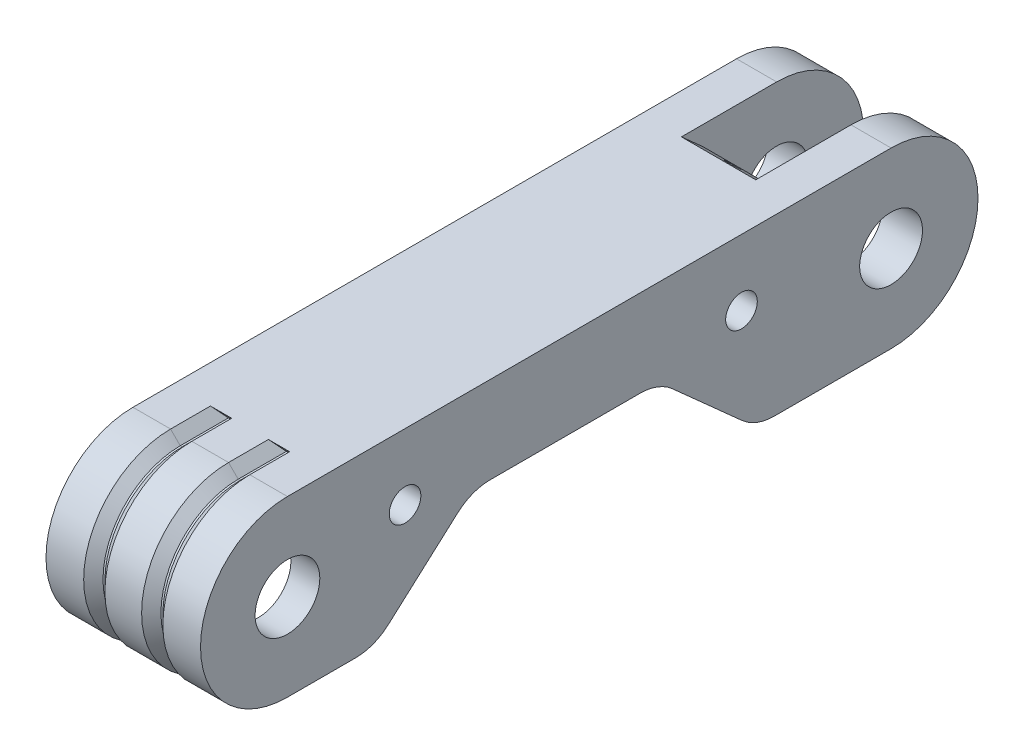
SolidWorks part; units mm, degrees
material "ABS"
ref_plane "Front Plane" through (0, 0, 0) normal (0, 0, 1) x (1, 0, 0)
ref_plane "Top Plane" through (0, 0, 0) normal (0, 1, 0) x (1, 0, 0)
ref_plane "Right Plane" through (0, 0, 0) normal (1, 0, 0) x (0, 0, -1)
ref_plane "Plane4" through (-3, 0, 0) normal (1, 0, 0) x (0, 0, -1)
sketch "Sketch1" plane through (0, 0, 0) normal (1, 0, 0) x (0, 0, -1)
  line L0 (0, 0) -> (62.5, 0) construction
  line L1 (0, 9) -> (62.5, 9)
  line L2 (0, -9) -> (62.5, -9)
  circle A0 centre (0, 0) radius 3.35
  circle A1 centre (62.5, 0) radius 3.25
  arc A2 (0, 9) -> (0, -9) centre (0, 0) ccw
  arc A3 (62.5, 9) -> (62.5, -9) centre (62.5, 0) cw
  dimension "D1" = 6.7
  dimension "D4" = 6.5
  dimension "D2" = 62.5
  dimension "D3" = 18
extrude "Finger Frame" add sketch "Sketch1" along normal mid plane 16
sketch "Sketch2" plane through (0, 0, 0) normal (1, 0, 0) x (0, 0, -1)
  line L0 (62.5, 9) -> (0, 9) construction
  line L1 (62.5, 9) -> (0, 9) construction
  line L2 (52.6402, 9) -> (55.6217, 6.3333)
  line L3 (62.5, 0) -> (0, 0) construction
  line L4 (62.5, 0) -> (55.8886, -6.6114) construction
  line L5 (55.8886, -6.6114) -> (53.15, -9.35)
  line L6 (53.15, -9.35) -> (62.5, -9.35)
  line L7 (62.5, 9.35) -> (52.6402, 9.35)
  line L8 (52.6402, 9.35) -> (52.6402, 9)
  circle A0 centre (62.5, 0) radius 9 construction
  arc A1 (62.5, -9) -> (62.5, 9) centre (62.5, 0) ccw construction
  circle A2 centre (62.5, 0) radius 9.35 construction
  arc A3 (55.6217, 6.3333) -> (55.8886, -6.6114) centre (62.5, 0) ccw
  arc A4 (62.5, 9.35) -> (62.5, -9.35) centre (62.5, 0) cw
  point P11 (53.7583, 8)
  dimension "D1" = 0.35
  dimension "D2" = 8
  dimension "D3" = 1.5
  dimension "D4" = 45
  dimension "D5" = 2.5
extrude "Routing Feature" cut sketch "Sketch2" against normal mid plane 7.7
sketch "Sketch3" plane through (8, 0, 0) normal (1, 0, 0) x (0, 0, -1)
  line L0 (52.6402, 9) -> (55.6217, 6.3333) construction
  line L1 (52.6402, 9) -> (55.6217, 6.3333) construction
  line L2 (54.131, 7.6667) -> (38.6499, -9.6417) construction
  line L3 (12.175, 2.1625) -> (47.0109, 2.1625) construction
  line L4 (62.5, 9) -> (0, 9) construction
  circle A0 centre (47.0109, 2.1625) radius 1.6375
  circle A1 centre (12.175, 2.1625) radius 1.6375
  arc A2 (55.6217, 6.3333) -> (55.8886, -6.6114) centre (62.5, 0) ccw construction
  arc A3 (55.6217, 6.3333) -> (55.8886, -6.6114) centre (62.5, 0) ccw construction
  circle A4 centre (0, 0) radius 9 construction
  arc A5 (0, 9) -> (0, -9) centre (0, 0) ccw construction
  point P19 (10.5375, 2.1625)
  point P20 (9, 0)
  dimension "D1" = 3.275
  dimension "D2" = 6.8375
  dimension "D3" = 3.175
extrude "Routing Pins" cut sketch "Sketch3" against normal through all
sketch "Sketch7" plane through (0, 31.1571, -27.8678) normal (0, 0.7454, -0.6667) x (1, 0, 0)
  line L0 (0, 33.2357) -> (0, 37.2357) construction
  line L1 (-3.85, 33.2357) -> (3.85, 33.2357) construction
  line L2 (-3.85, 37.2357) -> (3.85, 37.2357) construction
  circle A0 centre (0, 34.7357) radius 0.75
  dimension "D2" = 1.5
  dimension "D1" = 1.5
extrude "Tendon Port" [suppressed] cut sketch "Sketch7" against normal blind 0.75
chamfer "Tendon Port Chamfer" [suppressed] distance 0.75 angle 45
sketch "Sketch6" plane through (8, 0, 0) normal (1, 0, 0) x (0, 0, -1)
  line L0 (62.5, 9) -> (0, 9) construction
  line L1 (11.95, 11.95) -> (47.3902, 11.95)
  line L2 (9, 9) -> (50.3402, 9)
  line L3 (9, 0) -> (9, 9) construction
  line L4 (52.6402, 9) -> (55.6217, 6.3333) construction
  line L5 (52.6402, 9) -> (55.6217, 6.3333) construction
  arc A0 (9, 9) -> (11.95, 11.95) centre (11.95, 9) cw
  arc A1 (47.3902, 11.95) -> (50.3402, 9) centre (47.3902, 9) cw
  circle A2 centre (0, 0) radius 9 construction
  arc A3 (0, 9) -> (0, -9) centre (0, 0) ccw construction
  dimension "D1" = 2.95
  dimension "D2" = 2.3
extrude "Finger Pad Outline" add sketch "Sketch6" against normal up to surface (16 mm away) up to face at (-8, 2.1625, -13.8125)
sketch "Sketch5" plane through (8, 0, 0) normal (1, 0, 0) x (0, 0, -1)
  line L0 (9, -9) -> (19.0623, 0)
  line L1 (0, -9) -> (62.5, -9) construction
  line L2 (19.0623, 0) -> (38.4377, 0)
  line L3 (38.4377, 0) -> (48.5, -9)
  line L4 (48.5, -9) -> (9, -9)
  line L5 (12.175, 2.1625) -> (47.0109, 2.1625) construction
  line L6 (29.593, 2.1625) -> (29.593, 9) construction
  line L7 (62.5, 9) -> (50.3402, 9) construction
  line L8 (52.6402, 9) -> (55.6217, 6.3333) construction
  line L9 (52.6402, 9) -> (55.6217, 6.3333) construction
  line L10 (19.0623, 0) -> (0, 0) construction
  line L11 (9, 9) -> (9, -9) construction
  line L12 (53.5, -9) -> (62.5, -9) construction
  line L13 (53.5, -9) -> (62.5, -9) construction
  dimension "D1" = 5
extrude "Finger Outline" cut sketch "Sketch5" against normal through all
sketch "Sketch10" plane through (0, 0, 0) normal (1, 0, 0) x (0, 0, -1)
  line L0 (0, -5) -> (0, -9)
  line L1 (0.5007, 4.9749) -> (12.175, 3.8)
  line L2 (12.175, 3.8) -> (47.0109, 3.8)
  line L3 (48.5497, 1.6024) -> (44.6907, -9)
  line L4 (44.6907, -9) -> (0, -9)
  circle A0 centre (12.175, 2.1625) radius 1.6375 construction
  circle A1 centre (47.0109, 2.1625) radius 1.6375 construction
  circle A2 centre (12.175, 2.1625) radius 1.6375 construction
  arc A3 (48.5497, 1.6024) -> (47.0109, 3.8) centre (47.0109, 2.1625) ccw
  circle A4 centre (0, 0) radius 3.35 construction
  circle A5 centre (0, 0) radius 3.35 construction
  circle A6 centre (0, 0) radius 5 construction
  circle A7 centre (0, 0) radius 9 construction
  arc A8 (0, 9) -> (0, -9) centre (0, 0) ccw construction
  arc A9 (0, -5) -> (0.5007, 4.9749) centre (0, 0) cw
  dimension "D1" = 10
  dimension "D2" = 70
extrude "Back Cutaway" cut sketch "Sketch10" against normal mid plane 10
sketch "Sketch11" plane through (-3, 0, 0) normal (1, 0, 0) x (0, 0, -1)
  line L0 (0, 9) -> (4.1275, 9) construction
  line L1 (4.1275, 9) -> (10.9341, 1.0941) construction
  line L2 (0, 9) -> (4.1275, 9)
  line L3 (0, -8) -> (0, -9)
  line L4 (0, 8) -> (4.9884, 8)
  line L5 (4.9884, 8) -> (4.1275, 9)
  circle A0 centre (12.175, 2.1625) radius 1.6375 construction
  circle A1 centre (12.175, 2.1625) radius 1.6375 construction
  circle A2 centre (0, 0) radius 9 construction
  arc A3 (0, 9) -> (0, -9) centre (0, 0) ccw construction
  circle A4 centre (0, 0) radius 8 construction
  arc A5 (0, -9) -> (0, 9) centre (0, 0) cw
  arc A6 (0, -8) -> (0, 8) centre (0, 0) cw
  dimension "D1" = 16
extrude "Tendon Track" cut sketch "Sketch11" against normal mid plane 0.2
chamfer "Tendon Track Chamfer" distance 1 angle 45 4 edges at (-3.1, 0, 9) (-3.1, 9, -2.0637) (-2.9, 0, 9) (-2.9, 9, -2.0637)
sketch "Sketch19" plane through (0, -9, 0) normal (0, -1, 0) x (1, 0, 0)
  line L0 (0, -53.5) -> (0, -48.5) construction
  line L1 (-3.85, -53.5) -> (3.85, -53.5) construction
  line L2 (-8, -48.5) -> (8, -48.5) construction
  circle A0 centre (0, -51) radius 1.85
  dimension "D1" = 3.7
extrude "Distal Spring Anchor" cut sketch "Sketch19" against normal blind 4.5
fillet "Finger Contouring" radius 5 7 edges at (0, -9, -48.5) (6.5, 0, -38.4377) (-6.5, 0, -38.4377) (-6.5, 0, -19.0623) (6.5, 0, -19.0623) (-6.5, -9, -9) (6.5, -9, -9)
fillet "Contouring" radius 1 2 edges at (0, 6.3333, -55.6217) (0, -6.6114, -55.8886)
sketch "Sketch33" plane through (8, 0, 0) normal (1, 0, 0) x (0, 0, -1)
  circle A1 centre (0, 0) radius 3.35 construction
  circle A2 centre (12.175, 2.1625) radius 1.6375 construction
  circle A3 centre (47.0109, 2.1625) radius 1.6375 construction
  circle A4 centre (62.5, 0) radius 3.25 construction
  circle A5 centre (0, 0) radius 3.35
  circle A6 centre (12.175, 2.1625) radius 1.6375
  circle A7 centre (47.0109, 2.1625) radius 1.6375
  circle A8 centre (62.5, 0) radius 3.25
  circle A9 centre (0, 0) radius 3.7
  circle A10 centre (12.175, 2.1625) radius 1.7875
  circle A11 centre (47.0109, 2.1625) radius 1.7875
  circle A12 centre (62.5, 0) radius 3.4
  dimension "D1" = 0.35
  dimension "D2" = 0.15
  dimension "D3" = 0.15
  dimension "D4" = 0.15
extrude "Print Clearance - Pin" [suppressed] cut sketch "Sketch33" against normal through all
ref_point "Point1"
ref_plane "Plane3" through (0, 9, 0) normal (0, 1, 0) x (1, 0, 0)
other "SurfaceCut3" flip cut yes
pattern_linear "LPattern5" count 2 spacing 6 along (1, 0, 0) of "Tendon Track", "Tendon Track Chamfer"
sketch "Sketch34" plane through (0, 3.8, 0) normal (0, -1, 0) x (1, 0, 0)
  line L0 (-5, -28.75) -> (5, -28.75) construction
  line L1 (-5, -36.5279) -> (-5, -20.9721) construction
  line L2 (5, -36.5279) -> (5, -20.9721) construction
  line L3 (0, -12.175) -> (0, -45.6263) construction
  line L4 (-5, -12.175) -> (5, -12.175) construction
  line L5 (5, -45.6263) -> (-5, -45.6263) construction
  circle A0 centre (0, -28.75) radius 1.85
  dimension "D1" = 3.7
extrude "Cut-Extrude2" cut sketch "Sketch34" against normal blind 3.7
sketch "Sketch36" plane through (0, 0, 0) normal (1, 0, 0) x (0, 0, -1)
  line L0 (52.6402, 9) -> (55.6217, 6.3333) construction
  line L1 (54.131, 7.6667) -> (38.6499, -9.6417) construction
  line L2 (52.6402, 9) -> (55.6217, 6.3333)
  line L3 (54.131, 7.6667) -> (38.6499, -9.6417)
sketch "Sketch37" plane through (0, 31.1571, -27.8678) normal (0, 0.7454, -0.6667) x (1, 0, 0)
  circle A0 centre (0, 35.2357) radius 0.75
  dimension "D1" = 1.5
extrude "Cut-Extrude3" cut sketch "Sketch37" against normal blind 17
